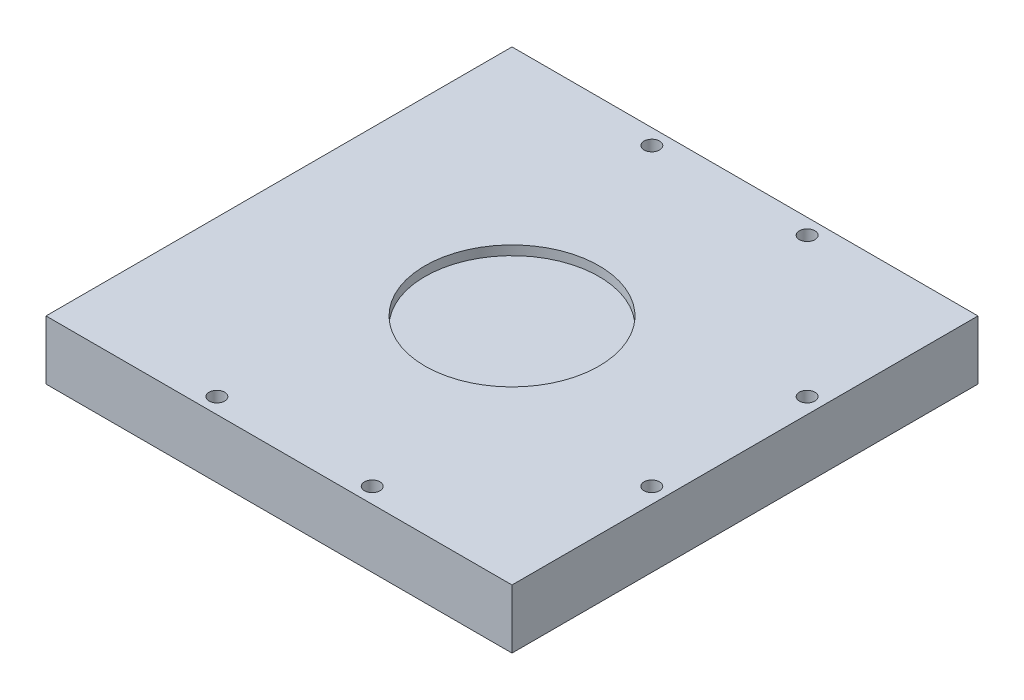
SolidWorks part; units mm, degrees
ref_plane "Front Plane" through (0, 0, 0) normal (0, 0, 1) x (1, 0, 0)
ref_plane "Top Plane" through (0, 0, 0) normal (0, 1, 0) x (1, 0, 0)
ref_plane "Right Plane" through (0, 0, 0) normal (1, 0, 0) x (0, 0, -1)
sketch "Sketch1" plane through (0, 0, 0) normal (0, 1, 0) x (1, 0, 0)
  line L1 (0, 0) -> (150, 0)
  line L2 (0, 0) -> (0, 150)
  line L3 (0, 150) -> (150, 150)
  line L4 (150, 0) -> (150, 150)
  dimension "D1" = 150
  dimension "D2" = 150
extrude "Boss-Extrude1" add sketch "Sketch1" along normal blind 19
sketch "Sketch2" plane through (0, 19, 0) normal (0, 1, 0) x (1, 0, 0)
  line L0 (75, 150) -> (75, 0) construction
  line L1 (150, 150) -> (0, 150) construction
  line L2 (0, 0) -> (150, 0) construction
  circle A0 centre (75, 75) radius 28
  dimension "D1" = 56
extrude "Cut-Extrude1" cut sketch "Sketch2" against normal blind 3
sketch "Sketch3" plane through (0, 19, 0) normal (0, 1, 0) x (1, 0, 0)
  line L1 (150, 0) -> (150, 150) construction
  line L2 (0, 0) -> (150, 0) construction
  line L3 (0, 150) -> (0, 0) construction
  circle A1 centre (100, 5) radius 2.5
  circle A2 centre (50, 5) radius 2.5
  dimension "D1" = 5
  dimension "D3" = 5
  dimension "D5" = 5
  dimension "D2" = 50
  dimension "D4" = 50
ref_point "Point1"
ref_axis "Axis1" through (75, 16, -75) along (0, 1, 0)
extrude "Cut-Extrude2" cut sketch "Sketch3" against normal blind 5
pattern_circular "CirPattern1" count 3 every 90 about axis through (75, 16, -75) along (0, 1, 0) of "Cut-Extrude2"
